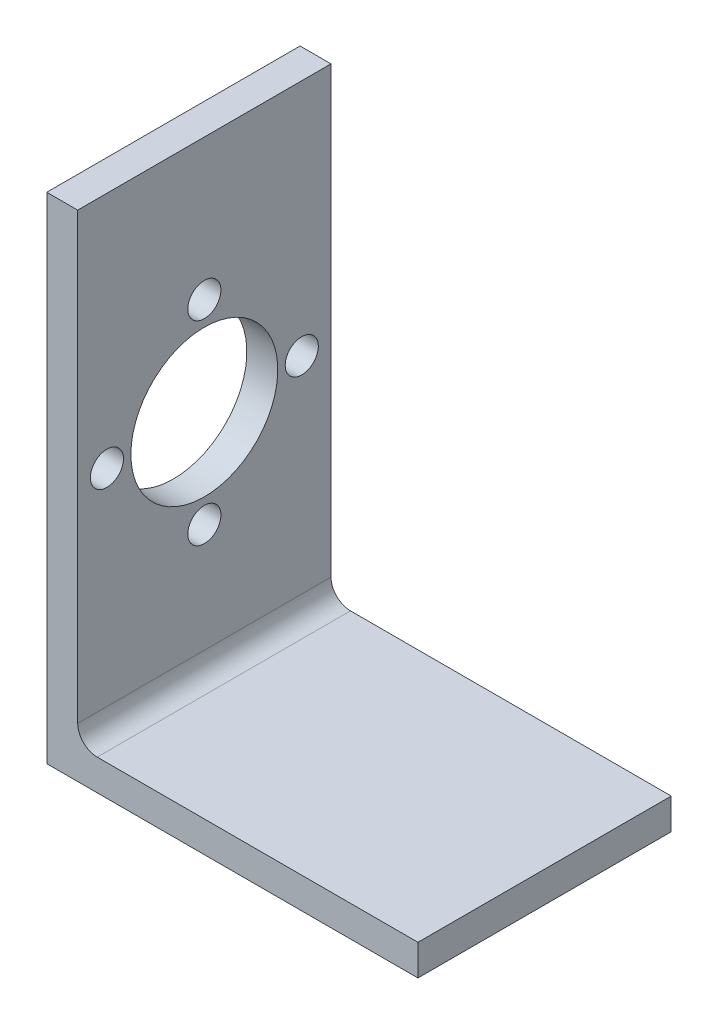
SolidWorks part; units mm, degrees
material "6061-T6 (SS)"
ref_plane "Front Plane" through (0, 0, 0) normal (0, 0, 1) x (1, 0, 0)
ref_plane "Top Plane" through (0, 0, 0) normal (0, 1, 0) x (1, 0, 0)
ref_plane "Right Plane" through (0, 0, 0) normal (1, 0, 0) x (0, 0, -1)
sketch "Sketch1" plane through (0, 0, 0) normal (0, 0, 1) x (1, 0, 0)
  line L0 (0, 0) -> (0, 50.8)
  line L1 (0, 50.8) -> (3.175, 50.8)
  line L2 (3.175, 50.8) -> (3.175, 3.175)
  line L3 (3.175, 3.175) -> (38.1, 3.175)
  line L4 (38.1, 3.175) -> (38.1, 0)
  line L5 (38.1, 0) -> (0, 0)
  dimension "D1" = 3.175
  dimension "D2" = 3.175
  dimension "D3" = 38.1
  dimension "D4" = 50.8
extrude "Boss-Extrude1" add sketch "Sketch1" along normal mid plane 26
fillet "Fillet1" radius 2 1 edges at (3.175, 3.175, 0)
sketch "Sketch5" plane through (0, 0, 0) normal (-1, 0, 0) x (0, 0, 1)
  line L0 (13, 0) -> (-13, 0) construction
  point P0 (0, 36.35)
  point P2 (10, 26.35)
  point P4 (-10, 26.35)
  point P6 (0, 16.35)
  dimension "D1" = 16.35
  dimension "D2" = 20
  dimension "D3" = 10
  dimension "D4" = 20
  dimension "D5" = 10
hole_wizard "M3 Clearance Hole1" positions "Sketch5" profile "Sketch3" hole size "M3" standard "ANSI Metric" end condition through all
sketch "Sketch3" plane through (0, 36.35, 0) normal (0, 1, 0) x (0, 0, 1)
  line L0 (0, 0) -> (0, 38.1)
  line L1 (0, 38.1) -> (1.7, 38.1)
  line L2 (1.7, 38.1) -> (1.7, 0)
  line L5 (1.7, 0) -> (0, 0)
  line L11 (0, -6.35) -> (0, 107.95) construction
  dimension "Thru Hole Dia." = 3.4
  dimension "Thru Hole Depth" = 38.1
sketch "Sketch6" plane through (0, 0, 0) normal (-1, 0, 0) x (0, 0, 1)
  circle A0 centre (0, 26.35) radius 7.54
  circle A2 centre (0, 16.35) radius 1.7 construction
  point P2 (0, 0)
  point P3 (0, 26.5497)
  point P5 (0, 0)
  dimension "D2" = 15.08
  dimension "D1" = 10
extrude "Cut-Extrude1" cut sketch "Sketch6" against normal through all
